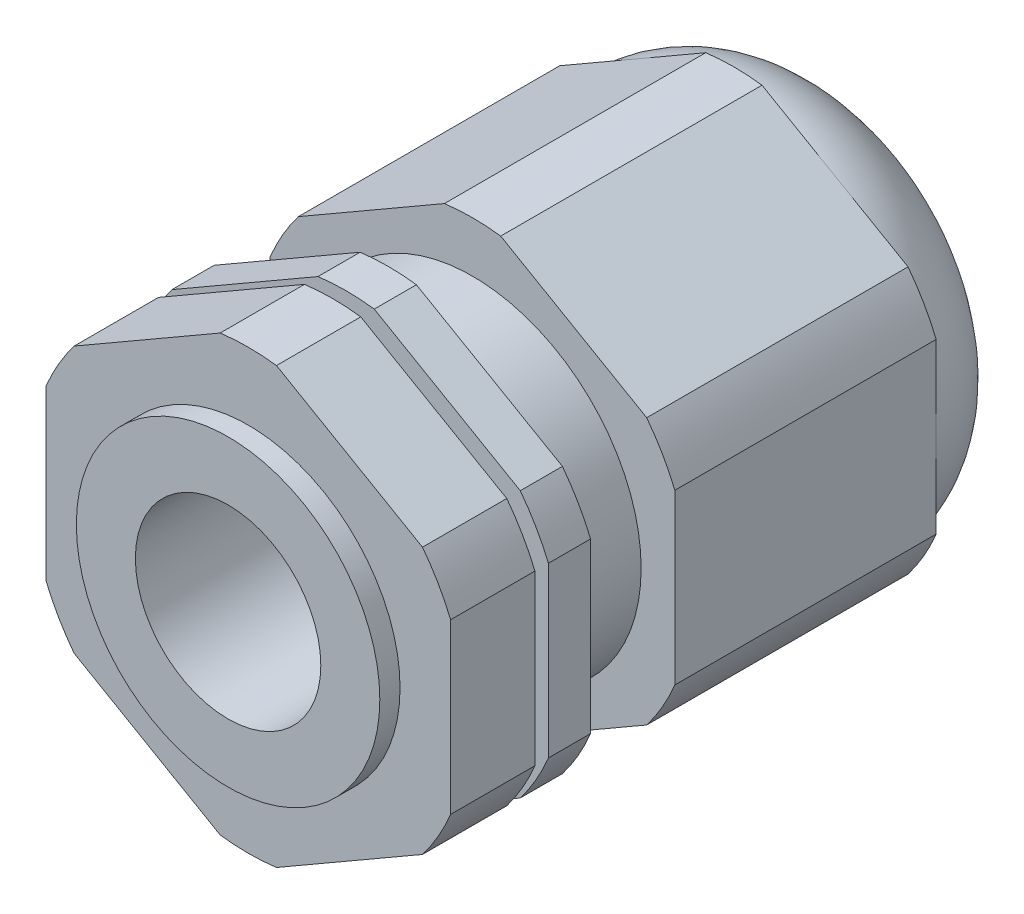
SolidWorks part; units mm, degrees
material "ABS"
ref_plane "Front Plane" through (0, 0, 0) normal (0, 0, 1) x (1, 0, 0)
ref_plane "Top Plane" through (0, 0, 0) normal (0, 1, 0) x (1, 0, 0)
ref_plane "Right Plane" through (0, 0, 0) normal (1, 0, 0) x (0, 0, -1)
sketch "Sketch1" plane through (0, 0, 0) normal (1, 0, 0) x (0, 0, -1)
  line L0 (-7, 0) -> (29, 0) construction
  line L1 (-7, 9) -> (-5.8, 9)
  line L2 (0, 9) -> (0, 13)
  line L7 (0, 13) -> (29, 13)
  line L8 (29, 13) -> (29, 5.5)
  line L9 (29, 5.5) -> (-7, 5.5)
  line L10 (-7, 5.5) -> (-7, 9)
  line L12 (-5.8, 9) -> (-5.8, 13)
  line L13 (-5.8, 13) -> (-0.8, 13)
  line L14 (-0.8, 13) -> (-0.8, 9)
  line L15 (-0.8, 9) -> (0, 9)
  dimension "D3" = 18
  dimension "D6" = 26
  dimension "D7" = 0.8
revolve "Revolve1" add sketch "Sketch1" angle 360 about L0
sketch "Sketch2" plane through (0, 0, 5.8) normal (0, 0, 1) x (1, 0, 0)
  line L1 (0, 13.8564) -> (-12, 6.9282)
  line L2 (-12, 6.9282) -> (-12, -6.9282)
  line L3 (-12, -6.9282) -> (0, -13.8564)
  line L4 (0, -13.8564) -> (12, -6.9282)
  line L5 (12, -6.9282) -> (12, 6.9282)
  line L6 (12, 6.9282) -> (0, 13.8564)
  circle A0 centre (0, 0) radius 12 construction
extrude "Cut-Extrude1" cut sketch "Sketch2" against normal through all flip side to cut
sketch "Sketch3" plane through (0, 0, 0) normal (0, 1, 0) x (1, 0, 0)
  line L0 (-12, 0) -> (-12, 29) construction
  line L1 (-1.6699, 29) -> (-10.3301, 29) construction
  line L2 (0, 29) -> (0, 0) construction
  line L3 (1.6699, 29) -> (-1.6699, 29) construction
  line L4 (-6, 29) -> (-6, 34)
  line L5 (-6, 34) -> (-61.4469, 34)
  line L6 (-61.4469, 34) -> (-61.4469, 23)
  line L7 (-61.4469, 23) -> (-12, 23)
  line L8 (-12, 0) -> (-12, 29) construction
  line L9 (-14, 7.5) -> (-10, 7.5)
  line L10 (-14, 7.5) -> (-14, 2.5)
  line L11 (-14, 2.5) -> (-10, 2.5)
  line L12 (-10, 7.5) -> (-10, 2.5)
  line L13 (-14, 7.5) -> (-10, 2.5) construction
  line L14 (-14, 2.5) -> (-10, 7.5) construction
  line L15 (-9, 0) -> (-9, -0.8) construction
  line L16 (-12, -5.8) -> (-12, -0.8) construction
  line L17 (-12, 2.5) -> (-12, 0) construction
  line L18 (-12, -3.3) -> (-12, -5.8) construction
  arc A0 (-12, 23) -> (-6, 29) centre (-6, 23) cw
  point P9 (-12, 5)
  dimension "D1" = 5
  dimension "D2" = 1
revolve "Cut-Revolve3" cut sketch "Sketch3" angle 360 about L2
equation "\"B\"= 24"
equation "\"D\"= 18"
equation "\"D1\"= 11"
equation "\"D2\"= 26"
equation "\"L\"= 36"
equation "\"L1\"= 7"
equation "\"L2\"= 5"
equation "\"D1@Sketch2\"= \"B\""
equation "\"D3@Sketch1\"= \"D\""
equation "\"D4@Sketch1\"= \"D1\""
equation "\"D6@Sketch1\"= \"D2\""
equation "\"D1@Sketch1\"= \"L\""
equation "\"D2@Sketch1\"= \"L1\""
equation "\"D8@Sketch1\"= \"L2\""
